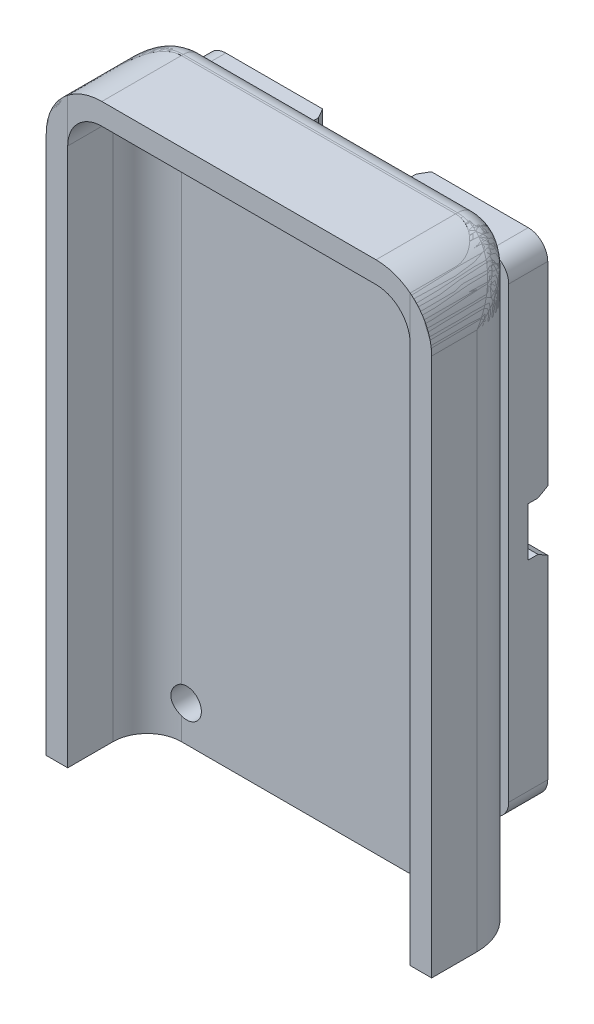
SolidWorks part; units mm, degrees
note: '?' marks a value the reader was unsure of.
ref_plane "Piano frontale" through (0, 0, 0) normal (0, 0, 1) x (1, 0, 0)
ref_plane "Piano superiore" through (0, 0, 0) normal (0, 1, 0) x (1, 0, 0)
ref_plane "Piano destro" through (0, 0, 0) normal (1, 0, 0) x (0, 0, -1)
sketch "Schizzo1" plane through (0, 0, 0) normal (0, 0, 1) x (1, 0, 0)
  line L1 (-17.5, -25) -> (17.5, -25)
  line L2 (-17.5, -25) -> (-17.5, 25)
  line L3 (-17.5, 25) -> (17.5, 25)
  line L4 (17.5, -25) -> (17.5, 25)
  line L5 (-17.5, -25) -> (17.5, 25) construction
  line L6 (-17.5, 25) -> (17.5, -25) construction
  point P0 (0, 0)
  dimension "D1" = 35
  dimension "D2" = 50
extrude "Estrusione-Estrusione1" add sketch "Schizzo1" along normal mid plane 4 contours L3 L4 L1 L2
sketch "Schizzo2" plane through (0, 0, -2) normal (0, 0, -1) x (-1, 0, 0)
  line L0 (17.5, 25) -> (-17.5, 25) construction
  line L1 (-5, -25) -> (5, -25)
  line L2 (-5, -25) -> (-5, -2.5)
  line L3 (-5, 25) -> (5, 25)
  line L4 (5, -25) -> (5, -2.5)
  line L7 (17.5, -25) -> (17.5, 25) construction
  line L8 (-17.5, 2.5) -> (-5, 2.5)
  line L9 (-17.5, 2.5) -> (-17.5, -2.5)
  line L10 (-17.5, -2.5) -> (-5, -2.5)
  line L11 (17.5, 2.5) -> (17.5, -2.5)
  line L14 (5, 2.5) -> (17.5, 2.5)
  line L15 (5, 2.5) -> (5, 25)
  line L19 (-5, 2.5) -> (-5, 25)
  line L22 (5, -2.5) -> (17.5, -2.5)
  point P0 (0, 0)
  point P8 (0, 0)
  dimension "D1" = 10
  dimension "D2" = 5
extrude "Taglio-Estrusione1" cut sketch "Schizzo2" against normal blind 2
fillet "Raccordo1" radius 2 8 edges at (17.5, -25, 0) (-17.5, 25, 0) (-17.5, -25, 0) (-5, 2.5, -1) (-5, -2.5, -1) (5, -2.5, -1) (5, 2.5, -1) (17.5, 25, 0)
chamfer "Smusso1" distance 1 angle 30 12 edges at (-5, 14.75, -2) (-5.5858, 3.0858, -2) (-12.25, 2.5, -2) (-12.25, -2.5, -2) (-5.5858, -3.0858, -2) (-5, -14.75, -2) (5, -14.75, -2) (5.5858, -3.0858, -2) (12.25, -2.5, -2) (12.25, 2.5, -2) (5.5858, 3.0858, -2) (5, 14.75, -2)
ref_point "Punto1"
ref_axis "Assi1" through (0, 0, 2) along (0, -1, 0)?
sketch "Schizzo3" plane through (0, 25, 0) normal (0, 1, 0) x (1, 0, 0)
  line L0 (-17.55, -12.15) -> (-17.55, -7.5) construction
  line L1 (-14.05, -4) -> (14.05, -4) construction
  line L2 (17.55, -7.5) -> (17.55, -12.15) construction
  line L3 (-17.55, -12.15) -> (-17.55, -7.5)
  line L4 (-14.05, -4) -> (14.05, -4)
  line L5 (17.55, -7.5) -> (17.55, -12.15)
  line L6 (-19.75, -12.15) -> (-19.75, -7.5)
  line L7 (-14.05, -1.8) -> (14.05, -1.8)
  line L8 (19.75, -7.5) -> (19.75, -12.15)
  line L9 (19.75, -12.15) -> (17.55, -12.15)
  line L10 (-17.55, -12.15) -> (-19.75, -12.15)
  arc A0 (-14.05, -4) -> (-17.55, -7.5) centre (-14.05, -7.5) ccw construction
  arc A1 (17.55, -7.5) -> (14.05, -4) centre (14.05, -7.5) ccw construction
  arc A2 (-14.05, -4) -> (-17.55, -7.5) centre (-14.05, -7.5) ccw
  arc A3 (17.55, -7.5) -> (14.05, -4) centre (14.05, -7.5) ccw
  arc A4 (-14.05, -1.8) -> (-19.75, -7.5) centre (-14.05, -7.5) ccw
  arc A5 (19.75, -7.5) -> (14.05, -1.8) centre (14.05, -7.5) ccw
  dimension "D1" = 2.2
extrude "Estrusione-Estrusione6" add sketch "Schizzo3" against normal up to surface (61.3 mm away) from offset 3.9 contours L10 L6 A4 L7 A5 L8 L9 L5 A3 L4 A2 L3
sketch "Schizzo7" plane through (0, 0, 4) normal (0, 0, 1) x (1, 0, 0)
  line L0 (14.05, 26.3) -> (-14.05, 26.3) construction
  line L1 (14.05, 26.3) -> (-14.05, 26.3)
  line L2 (14.05, 28.5) -> (-14.05, 28.5)
  line L3 (17.55, 22.8) -> (19.75, 22.8)
  line L4 (-17.55, 22.8) -> (-19.75, 22.8)
  arc A0 (17.55, 22.8) -> (14.05, 26.3) centre (14.05, 22.8) ccw construction
  arc A1 (-14.05, 26.3) -> (-17.55, 22.8) centre (-14.05, 22.8) ccw construction
  arc A2 (17.55, 22.8) -> (14.05, 26.3) centre (14.05, 22.8) ccw
  arc A3 (-14.05, 26.3) -> (-17.55, 22.8) centre (-14.05, 22.8) ccw
  arc A4 (19.75, 22.8) -> (14.05, 28.5) centre (14.05, 22.8) ccw
  arc A5 (-14.05, 28.5) -> (-19.75, 22.8) centre (-14.05, 22.8) ccw
  dimension "D1" = 2.2
sketch "Schizzo6" plane through (0, 0, 4) normal (0, 0, 1) x (1, 0, 0)
  circle A0 centre (-13.5, -28.7) radius 1.5 construction
  circle A1 centre (13.5, -28.7) radius 1.5 construction
  circle A2 centre (-13.5, -28.7) radius 1.5
  circle A3 centre (13.5, -28.7) radius 1.5
extrude "Taglio-Estrusione2" cut sketch "Schizzo6" against normal through all both and the other way through all
extrude "Estrusione-Estrusione11" add sketch "Schizzo7" against normal up to surface (10.15 mm away) from surface at -2 separate body
sketch "Schizzo8" plane through (0, -32.4, 0) normal (0, -1, 0) x (1, 0, 0)
  line L0 (14.05, 1.8) -> (14.05, -2.2)
  line L1 (19.75, 7.5) -> (23.75, 7.5)
  line L2 (-19.75, 7.5) -> (-23.75, 7.5)
  line L3 (-14.05, 1.8) -> (-14.05, -2.2)
  arc A0 (-19.75, 7.5) -> (-14.05, 1.8) centre (-14.05, 7.5) ccw construction
  arc A1 (14.05, 1.8) -> (19.75, 7.5) centre (14.05, 7.5) ccw construction
  arc A2 (-19.75, 7.5) -> (-14.05, 1.8) centre (-14.05, 7.5) ccw
  arc A3 (14.05, 1.8) -> (19.75, 7.5) centre (14.05, 7.5) ccw
  arc A4 (14.05, -2.2) -> (23.75, 7.5) centre (14.05, 7.5) ccw
  arc A5 (-23.75, 7.5) -> (-14.05, -2.2) centre (-14.05, 7.5) ccw
  dimension "D1" = 4
extrude "Taglio-Estrusione5" cut sketch "Schizzo8" against normal through all both and the other way through all from surface at -57.4 starting at face at (0, 25, -0.2099)
fillet "Raccordo9" radius 2 5 edges at (18.5789, 26.2611, 4.0389) (14.805, 28.4498, 2) (-18.5789, 26.2611, 4.0389) (-14.805, 28.4498, 2) (0, 28.5, 2)
ref_plane "Piano1" through (0, 22.8, 0) normal (0, -1, 0) x (-1, 0, 0)
fillet "Fillet1" radius 2 5 edges at (0, 28.9, 1.8) (18.0805, 28.9, 3.4695) (-18.0805, 28.9, 3.4695) (19.75, 28.9, 9.825) (-19.75, 28.9, 9.825)
sketch "Sketch3" plane through (0, 0, 12.15) normal (0, 0, 1) x (1, 0, 0)
  line L1 (14.05, 28.5) -> (-14.05, 28.5) construction
  line L2 (14.05, 28.5) -> (-14.05, 28.5)
  line L3 (14.05, 31.5) -> (-14.05, 31.5)
  line L4 (19.75, 22.8) -> (22.75, 22.8)
  line L5 (-19.75, 22.8) -> (-22.75, 22.8)
  arc A0 (19.75, 22.8) -> (14.05, 28.5) centre (14.05, 22.8) ccw construction
  arc A1 (19.75, 22.8) -> (14.05, 28.5) centre (14.05, 22.8) ccw
  arc A2 (-14.05, 28.5) -> (-19.75, 22.8) centre (-14.05, 22.8) ccw construction
  arc A3 (-14.05, 28.5) -> (-19.75, 22.8) centre (-14.05, 22.8) ccw
  arc A4 (22.75, 22.8) -> (14.05, 31.5) centre (14.05, 22.8) ccw
  arc A5 (-14.05, 31.5) -> (-22.75, 22.8) centre (-14.05, 22.8) ccw
  dimension "D1" = 3
extrude "Cut-Extrude5" cut sketch "Sketch3" against normal through all both and the other way through all
fillet "Fillet2" radius 2 1 edges at (-19.2969, 25.027, 5.273)
